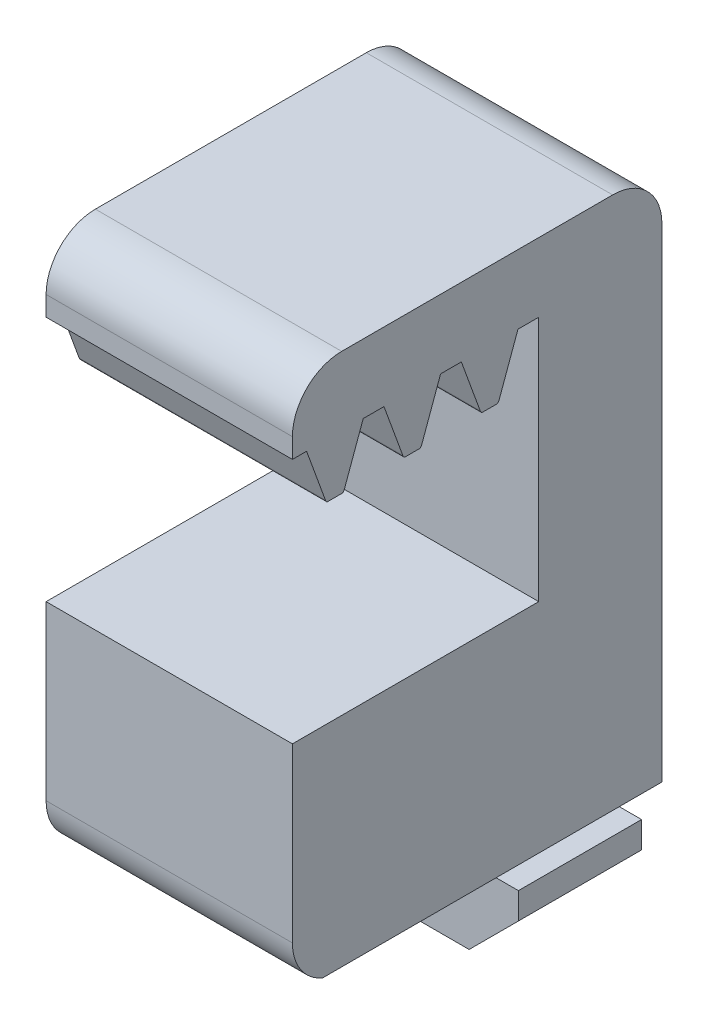
SolidWorks part; units mm, degrees
ref_plane "Front Plane" through (0, 0, 0) normal (0, 0, 1) x (1, 0, 0)
ref_plane "Top Plane" through (0, 0, 0) normal (0, 1, 0) x (1, 0, 0)
ref_plane "Right Plane" through (0, 0, 0) normal (1, 0, 0) x (0, 0, -1)
sketch "Sketch1" plane through (0, 0, 0) normal (1, 0, 0) x (0, 0, -1)
  line L0 (12.7, 0) -> (12.7, -6.096)
  line L1 (0, 27.686) -> (12.7, 27.686)
  line L2 (0, 27.686) -> (0, 21.336)
  line L3 (0, 21.336) -> (12.7, 21.336)
  line L5 (12.7, 27.686) -> (19.05, 27.686)
  line L6 (12.7, 21.336) -> (12.7, 11.43)
  line L7 (12.7, -6.096) -> (19.05, -6.096)
  line L8 (19.05, 27.686) -> (19.05, -6.096)
  line L9 (12.7, 11.43) -> (0, 11.43)
  line L11 (12.7, 0) -> (0, 0)
  line L12 (0, 11.43) -> (0, 0)
  dimension "D1" = 6.35
  dimension "D2" = 11.43
  dimension "D3" = 9.906
  dimension "D4" = 6.35
  dimension "D5" = 12.7
  dimension "D6" = 6.096
extrude "Boss-Extrude1" add sketch "Sketch1" along normal mid plane 12.7
sketch "Sketch2" plane through (6.35, 0, 0) normal (1, 0, 0) x (0, 0, -1)
  line L0 (3.6499, 24.13) -> (4.7203, 24.13) construction
  line L1 (5.6948, 21.4527) -> (4.7203, 24.13) construction
  line L2 (6.4261, 21.2852) -> (5.934, 21.2852) construction
  line L3 (7.6397, 24.13) -> (6.6653, 21.4527) construction
  line L4 (7.6397, 24.13) -> (8.7102, 24.13) construction
  line L5 (9.6846, 21.4527) -> (8.7102, 24.13) construction
  line L6 (10.4159, 21.2852) -> (9.9238, 21.2852) construction
  line L7 (11.6296, 24.13) -> (10.6551, 21.4527) construction
  line L8 (11.6296, 24.13) -> (12.7, 24.13) construction
  line L9 (3.6499, 24.13) -> (4.7203, 24.13)
  line L10 (5.6948, 21.4527) -> (4.7203, 24.13)
  line L11 (6.4261, 21.2852) -> (5.934, 21.2852)
  line L12 (7.6397, 24.13) -> (6.6653, 21.4527)
  line L13 (7.6397, 24.13) -> (8.7102, 24.13)
  line L14 (9.6846, 21.4527) -> (8.7102, 24.13)
  line L15 (10.4159, 21.2852) -> (9.9238, 21.2852)
  line L16 (11.6296, 24.13) -> (10.6551, 21.4527)
  line L17 (11.6296, 24.13) -> (12.7, 24.13)
  line L18 (12.7, 24.13) -> (12.7, 11.43)
  line L19 (12.7, 21.336) -> (12.7, 11.43) construction
  line L20 (12.7, 11.43) -> (3.6499, 11.43)
  line L21 (3.6499, 11.43) -> (3.6499, 24.13)
  line L22 (12.7, 11.43) -> (0, 11.43) construction
  arc A0 (5.6948, 21.4527) -> (5.934, 21.2852) centre (5.934, 21.5398) ccw construction
  arc A1 (6.4261, 21.2852) -> (6.6653, 21.4527) centre (6.4261, 21.5398) ccw construction
  arc A2 (9.6846, 21.4527) -> (9.9238, 21.2852) centre (9.9238, 21.5398) ccw construction
  arc A3 (10.4159, 21.2852) -> (10.6551, 21.4527) centre (10.4159, 21.5398) ccw construction
  arc A4 (5.6948, 21.4527) -> (5.934, 21.2852) centre (5.934, 21.5398) ccw
  arc A5 (6.4261, 21.2852) -> (6.6653, 21.4527) centre (6.4261, 21.5398) ccw
  arc A6 (9.6846, 21.4527) -> (9.9238, 21.2852) centre (9.9238, 21.5398) ccw
  arc A7 (10.4159, 21.2852) -> (10.6551, 21.4527) centre (10.4159, 21.5398) ccw
extrude "Cut-Extrude1" cut sketch "Sketch2" against normal through all
pattern_linear "LPattern1" count 10 spacing 3.9898 along (0, 0, 1) of "Cut-Extrude1"
sketch "Sketch3" plane through (0, 0, -19.05) normal (0, 0, -1) x (-1, 0, 0)
  line L0 (-6.35, -6.096) -> (-2.8393, -6.1)
  line L1 (2.8393, -6.1) -> (5.5, -3.4393) construction
  line L2 (5.5, -3.4393) -> (5.5, -1.8) construction
  line L3 (5.5, -1.8) -> (3.125, -1.8) construction
  line L4 (3.125, -1.8) -> (3.125, -1.455) construction
  line L5 (3.125, -1.455) -> (4.58, 0) construction
  line L6 (15.42, 0) -> (4.58, 0) construction
  line L7 (-4.58, 0) -> (-9.5, 0) construction
  line L8 (-3.125, -1.455) -> (-4.58, 0) construction
  line L9 (-3.125, -1.8) -> (-3.125, -1.455) construction
  line L10 (-5.5, -1.8) -> (-3.125, -1.8) construction
  line L11 (-5.5, -3.4393) -> (-5.5, -1.8) construction
  line L12 (-2.8393, -6.1) -> (-5.5, -3.4393) construction
  line L13 (2.8393, -6.1) -> (6.35, -6.096)
  line L15 (2.8393, -6.1) -> (5.5, -3.4393)
  line L16 (5.5, -3.4393) -> (5.5, -1.8)
  line L17 (5.5, -1.8) -> (3.125, -1.8)
  line L18 (3.125, -1.8) -> (3.125, -1.455)
  line L19 (3.125, -1.455) -> (4.58, 0)
  line L20 (15.42, 0) -> (4.58, 0)
  line L21 (-4.58, 0) -> (-9.5, 0)
  line L22 (-3.125, -1.455) -> (-4.58, 0)
  line L23 (-3.125, -1.8) -> (-3.125, -1.455)
  line L24 (-5.5, -1.8) -> (-3.125, -1.8)
  line L25 (-5.5, -3.4393) -> (-5.5, -1.8)
  line L26 (-2.8393, -6.1) -> (-5.5, -3.4393)
  line L29 (-9.5, 0) -> (-6.35, -6.096)
  line L32 (6.35, -6.096) -> (15.42, 0)
extrude "Cut-Extrude2" cut sketch "Sketch3" against normal through all
fillet "Fillet1" radius 2.54 3 edges at (0, 0, 0) (0, 27.686, 0) (0, 27.686, -19.05)
sketch "Sketch5" plane through (0, 0, -19.05) normal (0, 0, -1) x (-1, 0, 0)
  line L0 (6.35, 0) -> (4.58, 0) construction
  line L1 (4.58, 0) -> (3.125, -1.455) construction
  line L2 (3.125, -1.455) -> (3.125, -1.8) construction
  line L3 (3.125, -1.8) -> (5.5, -1.8) construction
  line L4 (5.5, -1.8) -> (5.5, -3.4393) construction
  line L5 (5.5, -3.4393) -> (2.8433, -6.096) construction
  line L6 (-2.8433, -6.096) -> (2.8433, -6.096) construction
  line L7 (-2.8433, -6.096) -> (-5.5, -3.4393) construction
  line L8 (-5.5, -3.4393) -> (-5.5, -1.8) construction
  line L9 (-5.5, -1.8) -> (-3.125, -1.8) construction
  line L10 (-3.125, -1.8) -> (-3.125, -1.455) construction
  line L11 (-3.125, -1.455) -> (-4.58, 0) construction
  line L12 (-4.58, 0) -> (-6.35, 0) construction
  line L13 (6.35, 0) -> (4.58, 0)
  line L14 (4.58, 0) -> (3.125, -1.455)
  line L15 (3.125, -1.455) -> (3.125, -1.8)
  line L16 (3.125, -1.8) -> (5.5, -1.8)
  line L17 (5.5, -1.8) -> (5.5, -3.4393)
  line L18 (5.5, -3.4393) -> (2.8433, -6.096)
  line L19 (-2.8433, -6.096) -> (2.8433, -6.096)
  line L20 (-2.8433, -6.096) -> (-5.5, -3.4393)
  line L21 (-5.5, -3.4393) -> (-5.5, -1.8)
  line L22 (-5.5, -1.8) -> (-3.125, -1.8)
  line L23 (-3.125, -1.8) -> (-3.125, -1.455)
  line L24 (-3.125, -1.455) -> (-4.58, 0)
  line L25 (-4.58, 0) -> (-6.35, 0)
  line L26 (6.35, 0.1984) -> (4.4978, 0.1984)
  line L27 (4.4978, 0.1984) -> (2.9266, -1.3728)
  line L28 (2.9266, -1.3728) -> (2.9266, -1.9984)
  line L29 (2.9266, -1.9984) -> (5.3016, -1.9984)
  line L30 (5.3016, -1.9984) -> (5.3016, -3.3571)
  line L31 (5.3016, -3.3571) -> (2.7611, -5.8976)
  line L32 (-2.7611, -5.8976) -> (2.7611, -5.8976)
  line L33 (-2.7611, -5.8976) -> (-5.3016, -3.3571)
  line L34 (-5.3016, -3.3571) -> (-5.3016, -1.9984)
  line L35 (-5.3016, -1.9984) -> (-2.9266, -1.9984)
  line L36 (-2.9266, -1.9984) -> (-2.9266, -1.3728)
  line L37 (-2.9266, -1.3728) -> (-4.4978, 0.1984)
  line L38 (-4.4978, 0.1984) -> (-6.35, 0.1984)
  line L39 (6.35, 0) -> (6.35, 0.1984)
  line L40 (-6.35, 0) -> (-6.35, 0.1984)
  dimension "D1" = 0.1984
extrude "Cut-Extrude3" cut sketch "Sketch5" against normal through all
